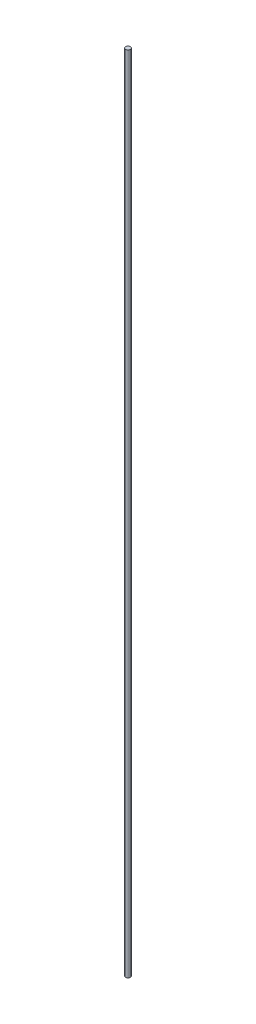
SolidWorks part; units mm, degrees
ref_plane "Спереди" through (0, 0, 0) normal (0, 0, 1) x (1, 0, 0)
ref_plane "Сверху" through (0, 0, 0) normal (0, 1, 0) x (1, 0, 0)
ref_plane "Справа" through (0, 0, 0) normal (1, 0, 0) x (0, 0, -1)
sketch "Эскиз2" plane through (0, 0, 0) normal (0, 0, 1) x (1, 0, 0)
  line L0 (0, 282.0757) -> (-5, 282.0757) construction
  line L5 (-2.5, 282.0757) -> (0, 282.0757)
  line L6 (-2.5, 282.0757) -> (-2.5, -557.7443)
  line L7 (-2.5, -557.7443) -> (0, -557.7443)
  line L8 (0, 282.0757) -> (0, -557.7443)
  line L9 (-2.5, 282.0757) -> (0, -557.7443) construction
  line L10 (-2.5, -557.7443) -> (0, 282.0757) construction
  line L13 (-506.5, -557.7443) -> (23.5, -557.7443) construction
  point P0 (-1.25, -137.8343)
  point P12 (0, 0)
  dimension "D1" = 2.5
revolve "Повернуть1" add sketch "Эскиз2" angle 360 about L6
equation "\"Ширина груза\"= 420"
equation "\"Глубина груза\"= 490"
equation "\"Высота груза\"= 297"
equation "\"Ширина ячейки\"= \"Ширина груза\" + 10"
equation "\"Глубина ячейки\"= \"Глубина груза\" + 10"
equation "\"Высота ячейки\"= \"Высота груза\" + 10 + 13"
equation "\"Колво ячеек ширина\"= 2"
equation "\"Колво ячеек высота\"= 2"
equation "\"Толщина стенки\"= 10"
equation "\"Крепление дверцы\"= 5"
equation "\"Ширина рейки\"= \"Толщина шестерни\""
equation "\"Высота рейки\"= 20"
equation "\"Высота пола\"= 20"
equation "\"Колво полозьев\"= 5"
equation "\"Отступ рейки\"= 20"
equation "\"Глубина каретки\"= \"Глубина ячейки\" + 30 + \"Мотор Y высота корпуса\" + 20"
equation "\"Длинна рейки\"= ( \"Ширина ячейки\" + \"Толщина стенки\" + \"Крепление дверцы\" ) * \"Колво ячеек ширина\" + \"Ширина ячейки выгрузки\" * \"Колво выгрузки\" + \"Толщина стенки\""
equation "\"Отступ шпильки\"= 26"
equation "\"Диаметр шпильки\"= 5"
equation "\"Длинна шпильки\"= ( \"Высота ячейки\" + \"Толщина стенки\" + \"Высота пола\" ) * \"Колво ячеек высота\" + ( \"Толщина стенки\" + \"Отступ рейки\" ) * 2 "
equation "\"D1@Эскиз2\"= \"Диаметр шпильки\" / 2"
equation "\"Ширина пластины\"= 50  "
equation "\"Высота зона выгрузки\"= \"Высота ячейки\" * 2 + \"Толщина стенки\" * 2"
equation "\"Колво выгрузки\"= 1"
equation "\"Отступ крепления мотора фиксации\" = 30"
equation "\"Мотор X ширина корпуса\"= 42.3"
equation "\"Мотор X высота корпуса\"= 42.3"
equation "\"Мотор X длина корпуса\"= 40"
equation "\"Мотор X вылет вала\"= 19.8"
equation "\"Мотор Y ширина корпуса\"= 42.3"
equation "\"Мотор Y высота корпуса\"= 42.3"
equation "\"Мотор Y длина корпуса\"= 48"
equation "\"Мотор Y вылет вала\"= 30"
equation "\"Мотор Z ширина корпуса\"= 42"
equation "\"Мотор Z высота корпуса\"= 42"
equation "\"Мотор Z длина корпуса\"= 40"
equation "\"Мотор Z вылет вала\"= 23"
equation "\"Мотор диаметр вала ПРЕДВ\"= 5"
equation "\"Мотор шаг крепления ПРЕДВ\"= 31"
equation "\"Мотор диаметр отверстий ПРЕДВ\"= 3"
equation "\"Мотор глубина отверстий ПРЕДВ\"= 4.5"
equation "\"Мотор диаметр буртика ПРЕДВ\"= 22"
equation "\"Мотор высота буртика ПРЕДВ\"= 2"
equation "\"Мотор диаметр шкива ПРЕДВ\"= 16"
equation "\"Мотор длина шкива ПРЕДВ\"= 12"
equation "\"Мотор отступ шкива ПРЕДВ\"= 5"
equation "\"Мотор X шаг градусов\"= 1.8"
equation "\"Мотор X ток А\"= 1.5"
equation "\"Мотор X сопротивление Ом\"= 1.3"
equation "\"Мотор X индуктивность мГн\"= 2"
equation "\"Мотор Y шаг градусов\"= 1.8"
equation "\"Мотор Y ток А\"= 2.2"
equation "\"Мотор Y сопротивление Ом\"= 0.9"
equation "\"Мотор Y индуктивность мГн\"= 2"
equation "\"Мотор Z шаг градусов\"= 1.8"
equation "\"Мотор Z ток А\"= 1"
equation "\"Мотор Z сопротивление Ом\"= 4"
equation "\"Мотор Z индуктивность мГн\"= 8"
equation "\"Мотор Y диаметр ротора\"= 25.78"
equation "\"Ширина ячейки выгрузки\"= \"Ширина ячейки\" + \"Толщина стенки\" + \"Отступ крепления мотора фиксации\"*2"
